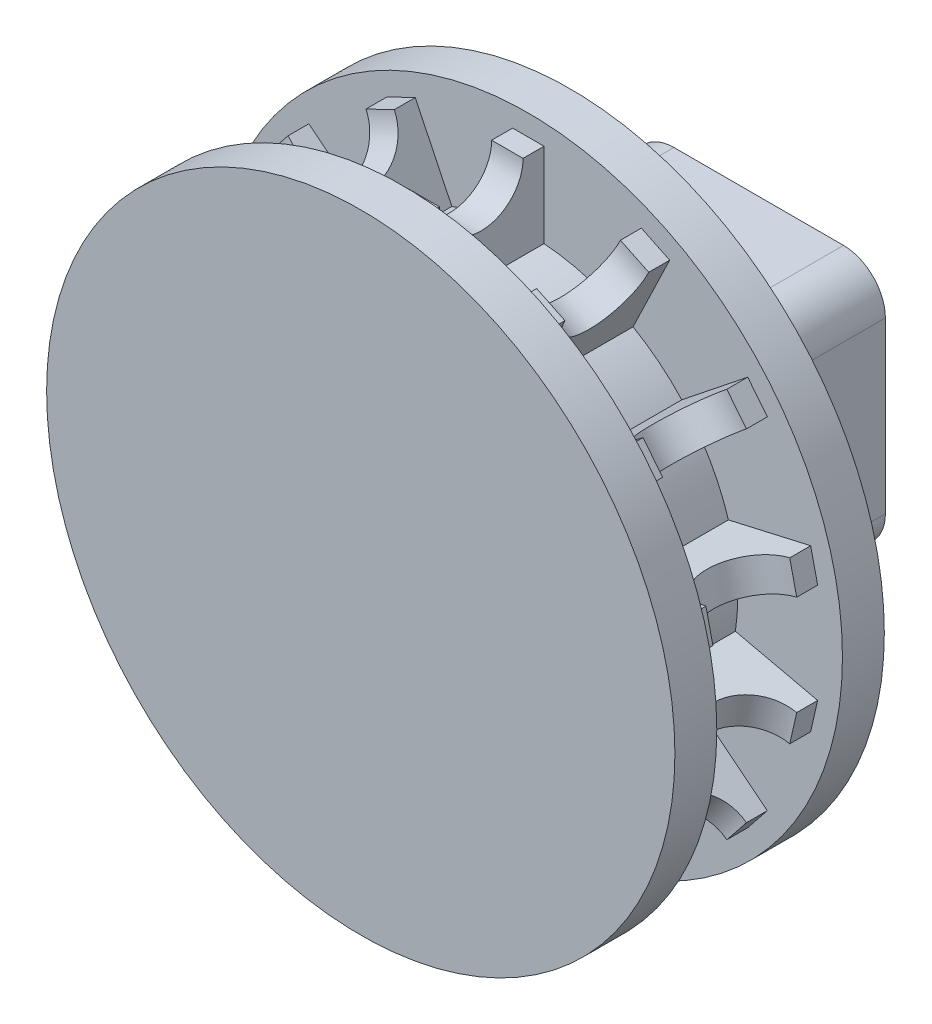
SolidWorks part; units mm, degrees
ref_plane "前基準面" through (0, 0, 0) normal (0, 0, 1) x (1, 0, 0)
ref_plane "上基準面" through (0, 0, 0) normal (0, 1, 0) x (1, 0, 0)
ref_plane "右基準面" through (0, 0, 0) normal (1, 0, 0) x (0, 0, -1)
ref_axis "基準軸1" through (0, 0, 5.5) along (0, 0, -1)
sketch "草圖1" plane through (0, 0, 0) normal (1, 0, 0) x (0, 0, -1)
  line L0 (-5, 0) -> (5, 0)
  line L1 (5, 0) -> (5, 15)
  line L2 (5, 15) -> (3, 15)
  line L3 (3, 15) -> (3, 10)
  line L4 (3, 10) -> (-3, 10)
  line L5 (-3, 10) -> (-3, 15)
  line L6 (-3, 15) -> (-5, 15)
  line L7 (-5, 15) -> (-5, 0)
  line L8 (0, 0) -> (0, 10) construction
  dimension "D1" = 10
  dimension "D2" = 2
  dimension "D3" = 15
  dimension "D4" = 10
revolve "旋轉1" add sketch "草圖1" angle 360 about L0
sketch "草圖2" plane through (0, 0, 0) normal (1, 0, 0) x (0, 0, -1)
  line L0 (-3, 10) -> (3, 10) construction
  line L1 (3, 10) -> (3, 14)
  line L2 (3, 15) -> (3, -15) construction
  line L3 (3, 14) -> (-3, 14) construction
  line L4 (-3, -15) -> (-3, 15) construction
  line L5 (-3, 14) -> (-3, 10)
  line L6 (-2, 14) -> (-3, 14)
  line L7 (2, 14) -> (3, 14)
  line L8 (-3, 10) -> (-3, 8.5)
  line L9 (-3, 8.5) -> (3, 8.5)
  line L10 (3, 8.5) -> (3, 10)
  arc A0 (-2, 14) -> (2, 14) centre (0, 14) ccw
  dimension "D2" = 2
  dimension "D1" = 4
  dimension "D3" = 1.5
extrude "填料-伸長1" add sketch "草圖2" along normal mid plane 1.5
pattern_circular "環狀複製排列1" count 14 over 360 about axis through (0, 0, 5.5) along (0, 0, -1) of "填料-伸長1"
sketch "草圖3" plane through (0, 0, -5) normal (0, 0, -1) x (-1, 0, 0)
  line L1 (-3.05, -3.05) -> (3.05, -3.05)
  line L2 (-3.05, -3.05) -> (-3.05, 3.05)
  line L3 (-3.05, 3.05) -> (3.05, 3.05)
  line L4 (3.05, -3.05) -> (3.05, 3.05)
  line L5 (-3.05, -3.05) -> (3.05, 3.05) construction
  line L6 (-3.05, 3.05) -> (3.05, -3.05) construction
  line L7 (-4.05, -6.05) -> (4.05, -6.05)
  line L8 (-6.05, -4.05) -> (-6.05, 4.05)
  line L9 (-4.05, 6.05) -> (4.05, 6.05)
  line L10 (6.05, -4.05) -> (6.05, 4.05)
  line L11 (-6.05, -6.05) -> (6.05, 6.05) construction
  line L12 (-6.05, 6.05) -> (6.05, -6.05) construction
  arc A0 (-4.05, -6.05) -> (-6.05, -4.05) centre (-4.05, -4.05) cw
  arc A1 (4.05, -6.05) -> (6.05, -4.05) centre (4.05, -4.05) ccw
  arc A2 (4.05, 6.05) -> (6.05, 4.05) centre (4.05, 4.05) cw
  arc A3 (-6.05, 4.05) -> (-4.05, 6.05) centre (-4.05, 4.05) cw
  point P0 (0, 0)
  point P6 (0, 0)
  dimension "D3" = 2
  dimension "D1" = 6.1
  dimension "D2" = 3
extrude "填料-伸長2" add sketch "草圖3" along normal blind 9
fillet "圓角1" radius 2 8 edges at (0, 6.05, -5) (-5.4642, 5.4642, -5) (-6.05, 0, -5) (-5.4642, -5.4642, -5) (0, -6.05, -5) (5.4642, -5.4642, -5) (6.05, 0, -5) (5.4642, 5.4642, -5)
chamfer "導角1" distance 0.2 angle 85 4 edges at (0, -3.05, -14) (-3.05, 0, -14) (0, 3.05, -14) (3.05, 0, -14) first distance on face at (0, 0, -14)
